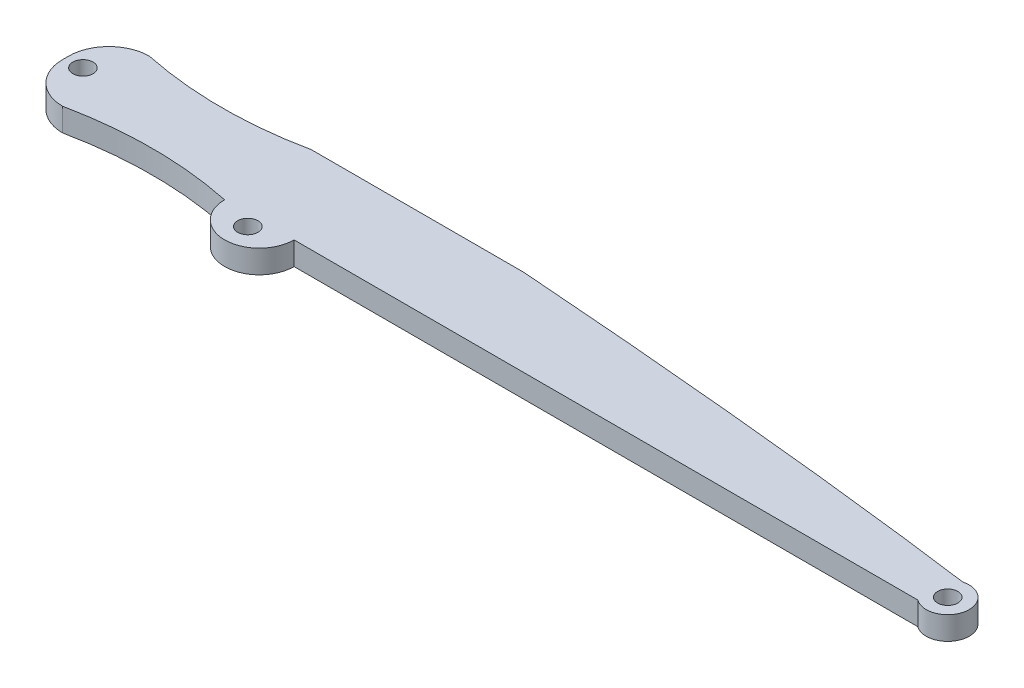
SolidWorks part; units mm, degrees
ref_plane "Front Plane" through (0, 0, 0) normal (0, 0, 1) x (1, 0, 0)
ref_plane "Top Plane" through (0, 0, 0) normal (0, 1, 0) x (1, 0, 0)
ref_plane "Right Plane" through (0, 0, 0) normal (1, 0, 0) x (0, 0, -1)
sketch "Sketch2" plane through (0, 0, 0) normal (0, 1, 0) x (1, 0, 0)
  line L11 (-80, 7.5) -> (80, 7.5)
  line L12 (-80, 7.5) -> (-80, -7.5)
  line L13 (-80, -7.5) -> (80, -7.5)
  line L14 (80, 7.5) -> (80, -7.5)
  dimension "D2" = 80
  dimension "D1" = 160
  dimension "D3" = 15
  dimension "D4" = 7.5
extrude "Boss-Extrude1" add sketch "Sketch2" along normal blind 4
sketch "Sketch4" plane through (0, 0, 0) normal (0, 1, 0) x (1, 0, 0)
  line L0 (-80, -7.5) -> (80, -7.5) construction
  line L1 (-45, -7.5) -> (-33, -7.5)
  arc A0 (-45, -7.5) -> (-33, -7.5) centre (-39, -7.5) ccw
  dimension "D1" = 6
  dimension "D2" = 35
  dimension "D3" = 12
extrude "Boss-Extrude2" add sketch "Sketch4" along normal up to surface (4 mm away) up to face at (0, 4, 0)
sketch "Sketch5" plane through (0, 4, 0) normal (0, 1, 0) x (1, 0, 0)
  line L0 (-80, -7.5) -> (-45, -7.5) construction
  line L1 (-80, 7.5) -> (-80, -7.5) construction
  line L2 (80, -7.5) -> (80, 7.5) construction
  line L3 (-33, -7.5) -> (80, -7.5) construction
  circle A0 centre (-77, 0) radius 1.75
  circle A1 centre (-39, -9.5) radius 1.75
  circle A2 centre (77, -4.5) radius 1.75
  arc A3 (-45, -7.5) -> (-33, -7.5) centre (-39, -7.5) ccw construction
  point P10 (-39, -13.5)
  dimension "D1" = 3.5
  dimension "D2" = 3.5
  dimension "D3" = 3.5
  dimension "D4" = 6
  dimension "D5" = 4
  dimension "D6" = 7.5
  dimension "D7" = 3
  dimension "D8" = 3
  dimension "D9" = 3
extrude "Cut-Extrude1" cut sketch "Sketch5" against normal through all
sketch "Sketch6" plane through (0, 4, 0) normal (0, 1, 0) x (1, 0, 0)
  line L2 (80, 7.5) -> (-8.2315, 7.5)
  line L3 (80, 7.5) -> (-80, 7.5) construction
  line L6 (-8.2315, 7.5) -> (14.2901, 5.8703) construction
  line L7 (14.2901, 5.8703) -> (49.5381, 2.8486) construction
  line L8 (49.5381, 2.8486) -> (69.508, -0.0694) construction
  line L9 (69.508, -0.0694) -> (80, -1.4494) construction
  line L10 (80, -7.5) -> (80, 7.5) construction
  line L11 (80, -1.4494) -> (80, 7.5)
  spline S0 degree 4 poles (-8.2315, 7.5) (14.2901, 5.8703) (49.5381, 2.8486) (69.508, -0.0694) (80, -1.4494) knots 0 0 0 0 0 1 1 1 1 1
  dimension "D1" = 88.6991
  dimension "D8" = 1.6297
  dimension "D2" = 88.2315
  dimension "D3" = 8.9494
  dimension "D4" = 10.5824
  dimension "D5" = 19.9699
  dimension "D6" = 22.5216
  dimension "D7" = 35.248
extrude "Cut-Extrude2" cut sketch "Sketch6" against normal through all
fillet "Fillet1" radius 7 2 edges at (-80, 2, -7.5) (-80, 2, 7.5)
fillet "Fillet2" radius 2 3 edges at (-8.2315, 2, -7.5) (80, 2, 7.5) (80, 2, 1.4494)
sketch "Sketch7" plane through (0, 4, 0) normal (0, 1, 0) x (1, 0, 0)
  line L0 (-73, -7.5) -> (-45, -7.5)
  line L1 (-73, -7.5) -> (-45, -7.5) construction
  line L2 (-73, 7.5) -> (-45, 7.5)
  line L3 (-8.3038, 7.5) -> (-73, 7.5) construction
  arc A1 (-45, -7.5) -> (-73, -7.5) centre (-59, -74.1454) ccw
  arc A2 (-73, 7.5) -> (-45, 7.5) centre (-59, 74.1454) ccw
  dimension "D1" = 68.1
  dimension "D2" = 28
  dimension "D3" = 68.1
extrude "Cut-Extrude3" cut sketch "Sketch7" against normal through all
sketch "Sketch8" plane through (0, 4, 0) normal (0, 1, 0) x (1, 0, 0)
  circle A0 centre (77, -4.5) radius 3.7056
  dimension "D1" = 7.4112
extrude "Boss-Extrude4" add sketch "Sketch8" against normal up to surface (4 mm away) up to face at (-77, 0, 1.75)
sketch "Sketch9" plane through (0, 4, 0) normal (0, 1, 0) x (1, 0, 0)
  circle A2 centre (77, -4.5) radius 1.75
extrude "Cut-Extrude4" cut sketch "Sketch9" against normal through all
